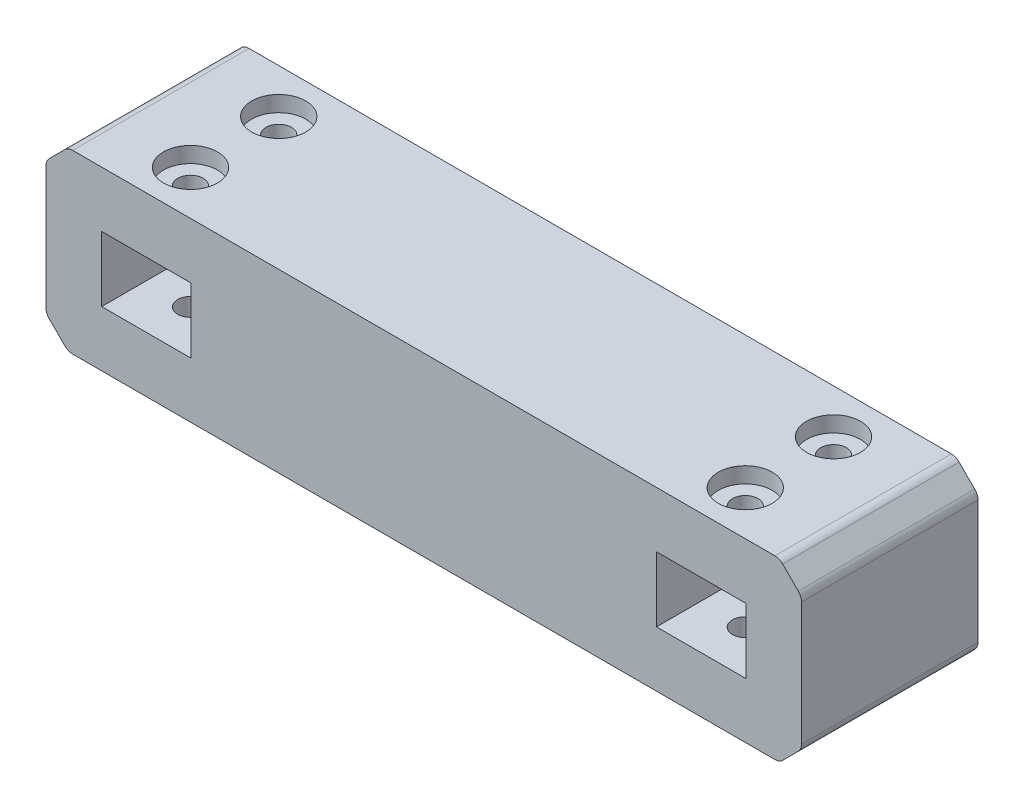
SolidWorks part; units mm, degrees
ref_plane "Front Plane" through (0, 0, 0) normal (0, 0, 1) x (1, 0, 0)
ref_plane "Top Plane" through (0, 0, 0) normal (0, 1, 0) x (1, 0, 0)
ref_plane "Right Plane" through (0, 0, 0) normal (1, 0, 0) x (0, 0, -1)
sketch "Sketch2" plane through (0, 0, 0) normal (0, 0, 1) x (1, 0, 0)
  line L1 (-85.625, 20) -> (85.625, 20)
  line L2 (-85.625, 20) -> (-85.625, -20)
  line L3 (-85.625, -20) -> (85.625, -20)
  line L4 (85.625, 20) -> (85.625, -20)
  line L5 (-85.625, 20) -> (85.625, -20) construction
  line L6 (-85.625, -20) -> (85.625, 20) construction
  point P0 (0, 0)
  dimension "D1" = 40
  dimension "D2" = 171.25
extrude "Boss-Extrude1" add sketch "Sketch2" along normal blind 40
sketch "Sketch3" plane through (0, 0, 40) normal (0, 0, 1) x (1, 0, 0)
  line L0 (22, 0) -> (-22, 0) construction
  line L5 (0, -22) -> (0, 22) construction
  line L6 (-52.75, -7.375) -> (-73, -7.375)
  line L7 (52.75, 7.375) -> (73, 7.375)
  line L8 (-52.75, -7.375) -> (-52.75, 7.375)
  line L13 (73, -7.375) -> (73, 7.375)
  line L14 (52.75, -7.375) -> (73, -7.375)
  line L15 (-52.75, 7.375) -> (-73, 7.375)
  line L16 (-73, -7.375) -> (-73, 7.375)
  line L17 (-52.75, -7.375) -> (-73, 7.375) construction
  line L18 (-52.75, 7.375) -> (-73, -7.375) construction
  line L28 (-85.625, 20) -> (-85.625, -20) construction
  line L29 (52.75, -7.375) -> (52.75, 7.375)
  point P0 (-62.875, 0)
  point P9 (50.625, 0)
  dimension "D1" = 22.75
  dimension "D2" = 20.25
  dimension "D3" = 14.75
extrude "Cut-Extrude1" cut sketch "Sketch3" against normal through all
chamfer "Chamfer1" distance 5 angle 45 4 edges at (85.625, 20, 20) (85.625, -20, 20) (-85.625, -20, 20) (-85.625, 20, 20)
fillet "Fillet1" radius 2.5 8 edges at (80.625, 20, 20) (85.625, 15, 20) (85.625, -15, 20) (80.625, -20, 20) (-80.625, -20, 20) (-85.625, -15, 20) (-80.625, 20, 20) (-85.625, 15, 20)
sketch "Sketch4" plane through (0, 20, 0) normal (0, 1, 0) x (1, 0, 0)
  line L0 (-85.625, -20) -> (-62.875, -20) construction
  line L1 (-85.625, -40) -> (-85.625, 0) construction
  line L2 (-62.875, -20) -> (-62.875, 0) construction
  line L3 (-22, 0) -> (22, 0) construction
  point P9 (-62.875, -10)
  dimension "D1" = 22.75
hole_wizard "CBORE for M5 Hex Head Bolt1" positions "Sketch4" profile "Sketch5" counterbore size "M5" standard "ANSI Metric" end condition through all
sketch "Sketch5" plane through (-62.875, 20, 10) normal (1, 0, 0) x (0, 0, 1)
  line L0 (0, 0) -> (0, 40)
  line L1 (0, 40) -> (2.9, 40)
  line L3 (2.9, 40) -> (2.9, 3.58)
  line L4 (2.9, 3.58) -> (6.12, 3.58)
  line L5 (6.12, 3.58) -> (6.12, 0)
  line L7 (6.12, 0) -> (0, 0)
  line L11 (0, -6.35) -> (0, 107.95) construction
  dimension "Thru Hole Dia." = 5.8
  dimension "Thru Hole Depth" = 40
  dimension "C'Bore Dia." = 12.24
  dimension "C'Bore Depth" = 3.58
ref_plane "Plane1" through (0, 0, 20) normal (0, 0, 1) x (1, 0, 0)
mirror "Mirror1" about plane through (0, 0, 20) normal (0, 0, 1) of "CBORE for M5 Hex Head Bolt1"
mirror "Mirror2" about plane through (0, 0, 0) normal (1, 0, 0) of "CBORE for M5 Hex Head Bolt1", "Mirror1"
equation "\"D2@Sketch2\"=2*45.5+80.25"
